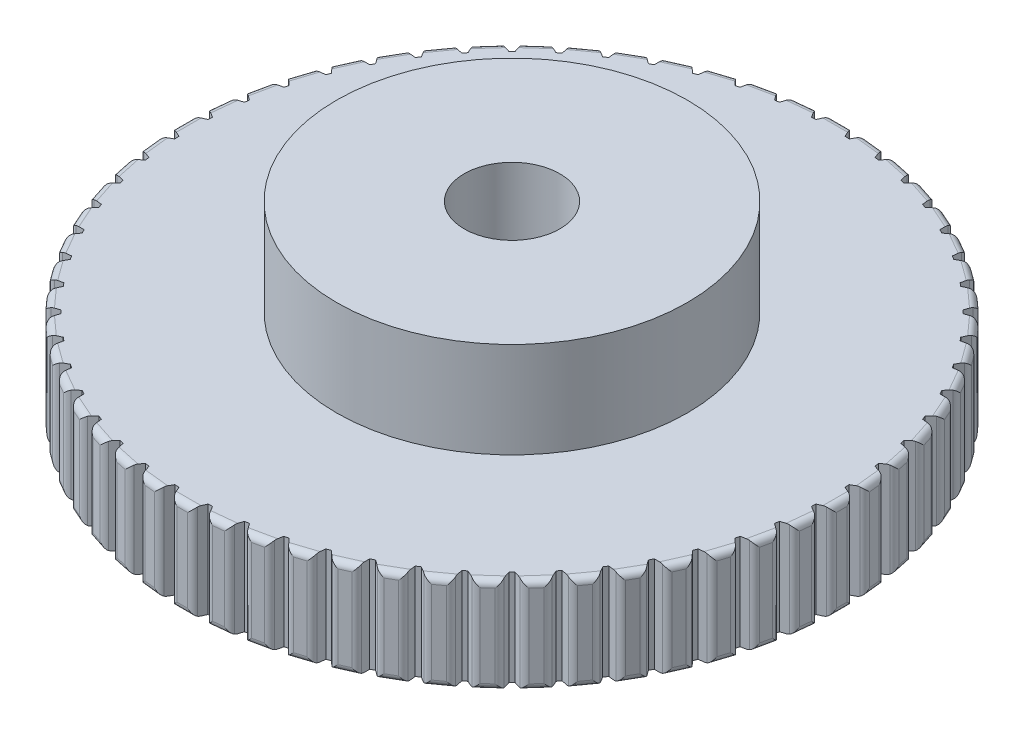
SolidWorks part; units mm, degrees
ref_plane "Front Plane" through (0, 0, 0) normal (0, 0, 1) x (1, 0, 0)
ref_plane "Top Plane" through (0, 0, 0) normal (0, 1, 0) x (1, 0, 0)
ref_plane "Right Plane" through (0, 0, 0) normal (1, 0, 0) x (0, 0, -1)
sketch "Sketch1" plane through (0, 0, 0) normal (0, 1, 0) x (1, 0, 0)
  line L0 (0, -65.659) -> (0, 65.659) construction
  line L1 (0, 65.659) -> (0, 85.595) construction
  line L2 (-1.905, 65.659) -> (1.905, 65.659)
  line L3 (-1.905, 65.659) -> (-3.2908, 62.5134)
  line L4 (-3.2908, 62.5134) -> (3.2908, 62.5134)
  line L5 (3.2908, 62.5134) -> (1.905, 65.659)
  circle A0 centre (0, 0) radius 65.659 construction
  circle A1 centre (0, 0) radius 63.5
  point P9 (0, 62.5134)
  dimension "D1" = 131.318
  dimension "D2" = 127
  dimension "D3" = 3.81
extrude "Boss-Extrude1" add sketch "Sketch1" along normal blind 19.05 contours L3 A1 L5 L4 | L5 A1 L3 L4 region at (0, 0, -62.9849) region at (0, 0, 0.0295)
extrude "Boss-Extrude2" add sketch "Sketch1<3>" along normal blind 19.05 contours A1 L5 L2 L3 region at (0, 0, -64.4954)
sketch "Sketch1<3>" plane through (0, 0, 0) normal (0, 1, 0) x (1, 0, 0) same geometry as "Sketch1"
pattern_circular "CirPattern1" count 60 over 360 about axis through (0, 19.05, 0) along (0, 1, 0) of "Boss-Extrude2"
fillet "Fillet4" radius 1.27 240 edges at (1.905, 9.525, -65.659) (0, 19.05, -65.659) (-1.905, 9.525, -65.659) (0, 0, -65.659) (-4.9687, 9.525, -65.4984) (-6.8632, 19.05, -65.2993) (-8.7578, 9.525, -65.1002) (-6.8632, 0, -65.2993) (-11.7879, 9.525, -64.6203) (-13.6513, 19.05, -64.2242) (-15.5146, 9.525, -63.8281) (-13.6513, 0, -64.2242) (-18.478, 9.525, -63.0341) (-20.2897, 19.05, -62.4454) (-22.1015, 9.525, -61.8567) (-20.2897, 0, -62.4454) (-24.9656, 9.525, -60.7573) (-26.7059, 19.05, -59.9825) (-28.4462, 9.525, -59.2076) (-26.7059, 0, -59.9825) (-31.1797, 9.525, -57.8149) (-32.8295, 19.05, -56.8624) (-34.4793, 9.525, -55.9099) (-32.8295, 0, -56.8624) (-37.0522, 9.525, -54.239) (-38.5934, 19.05, -53.1192) (-40.1346, 9.525, -51.9995) (-38.5934, 0, -53.1192) (-42.5188, 9.525, -50.0688) (-43.9344, 19.05, -48.7941) (-45.3501, 9.525, -47.5195) (-43.9344, 0, -48.7941) (-47.5195, 9.525, -45.3501) (-48.7941, 19.05, -43.9344) (-50.0688, 9.525, -42.5188) (-48.7941, 0, -43.9344) (-51.9995, 9.525, -40.1346) (-53.1192, 19.05, -38.5934) (-54.239, 9.525, -37.0522) (-53.1192, 0, -38.5934) (-55.9099, 9.525, -34.4793) (-56.8624, 19.05, -32.8295) (-57.8149, 9.525, -31.1797) (-56.8624, 0, -32.8295) (-59.2076, 9.525, -28.4462) (-59.9825, 19.05, -26.7059) (-60.7573, 9.525, -24.9656) (-59.9825, 0, -26.7059) (-61.8567, 9.525, -22.1015) (-62.4454, 19.05, -20.2897) (-63.0341, 9.525, -18.478) (-62.4454, 0, -20.2897) (-63.8281, 9.525, -15.5146) (-64.2242, 19.05, -13.6513) (-64.6203, 9.525, -11.7879) (-64.2242, 0, -13.6513) (-65.1002, 9.525, -8.7578) (-65.2993, 19.05, -6.8632) (-65.4984, 9.525, -4.9687) (-65.2993, 0, -6.8632) (-65.659, 9.525, -1.905) (-65.659, 19.05, 0) (-65.659, 9.525, 1.905) (-65.659, 0, 0) (-65.4984, 9.525, 4.9687) (-65.2993, 19.05, 6.8632) (-65.1002, 9.525, 8.7578) (-65.2993, 0, 6.8632) (-64.6203, 9.525, 11.7879) (-64.2242, 19.05, 13.6513) (-63.8281, 9.525, 15.5146) (-64.2242, 0, 13.6513) (-63.0341, 9.525, 18.478) (-62.4454, 19.05, 20.2897) (-61.8567, 9.525, 22.1015) (-62.4454, 0, 20.2897) (-60.7573, 9.525, 24.9656) (-59.9825, 19.05, 26.7059) (-59.2076, 9.525, 28.4462) (-59.9825, 0, 26.7059) (-57.8149, 9.525, 31.1797) (-56.8624, 19.05, 32.8295) (-55.9099, 9.525, 34.4793) (-56.8624, 0, 32.8295) (-54.239, 9.525, 37.0522) (-53.1192, 19.05, 38.5934) (-51.9995, 9.525, 40.1346) (-53.1192, 0, 38.5934) (-50.0688, 9.525, 42.5188) (-48.7941, 19.05, 43.9344) (-47.5195, 9.525, 45.3501) (-48.7941, 0, 43.9344) (-45.3501, 9.525, 47.5195) (-43.9344, 19.05, 48.7941) (-42.5188, 9.525, 50.0688) (-43.9344, 0, 48.7941) (-40.1346, 9.525, 51.9995) (-38.5934, 19.05, 53.1192) (-37.0522, 9.525, 54.239) (-38.5934, 0, 53.1192) (-34.4793, 9.525, 55.9099) (-32.8295, 19.05, 56.8624) (-31.1797, 9.525, 57.8149) (-32.8295, 0, 56.8624) (-28.4462, 9.525, 59.2076) (-26.7059, 19.05, 59.9825) (-24.9656, 9.525, 60.7573) (-26.7059, 0, 59.9825) (-22.1015, 9.525, 61.8567) (-20.2897, 19.05, 62.4454) (-18.478, 9.525, 63.0341) (-20.2897, 0, 62.4454) (-15.5146, 9.525, 63.8281) (-13.6513, 19.05, 64.2242) (-11.7879, 9.525, 64.6203) (-13.6513, 0, 64.2242) (-8.7578, 9.525, 65.1002) (-6.8632, 19.05, 65.2993) (-4.9687, 9.525, 65.4984) (-6.8632, 0, 65.2993) (-1.905, 9.525, 65.659) (0, 19.05, 65.659) (1.905, 9.525, 65.659) (0, 0, 65.659) (4.9687, 9.525, 65.4984) (6.8632, 19.05, 65.2993) (8.7578, 9.525, 65.1002) (6.8632, 0, 65.2993) (11.7879, 9.525, 64.6203) (13.6513, 19.05, 64.2242) (15.5146, 9.525, 63.8281) (13.6513, 0, 64.2242) (18.478, 9.525, 63.0341) (20.2897, 19.05, 62.4454) (22.1015, 9.525, 61.8567) (20.2897, 0, 62.4454) (24.9656, 9.525, 60.7573) (26.7059, 19.05, 59.9825) (28.4462, 9.525, 59.2076) (26.7059, 0, 59.9825) (31.1797, 9.525, 57.8149) (32.8295, 19.05, 56.8624) (34.4793, 9.525, 55.9099) (32.8295, 0, 56.8624) (37.0522, 9.525, 54.239) (38.5934, 19.05, 53.1192) (40.1346, 9.525, 51.9995) (38.5934, 0, 53.1192) (42.5188, 9.525, 50.0688) (43.9344, 19.05, 48.7941) (45.3501, 9.525, 47.5195) (43.9344, 0, 48.7941) (47.5195, 9.525, 45.3501) (48.7941, 19.05, 43.9344) (50.0688, 9.525, 42.5188) (48.7941, 0, 43.9344) (51.9995, 9.525, 40.1346) (53.1192, 19.05, 38.5934) (54.239, 9.525, 37.0522) (53.1192, 0, 38.5934) (55.9099, 9.525, 34.4793) (56.8624, 19.05, 32.8295) (57.8149, 9.525, 31.1797) (56.8624, 0, 32.8295) (59.2076, 9.525, 28.4462) (59.9825, 19.05, 26.7059) (60.7573, 9.525, 24.9656) (59.9825, 0, 26.7059) (61.8567, 9.525, 22.1015) (62.4454, 19.05, 20.2897) (63.0341, 9.525, 18.478) (62.4454, 0, 20.2897) (63.8281, 9.525, 15.5146) (64.2242, 19.05, 13.6513) (64.6203, 9.525, 11.7879) (64.2242, 0, 13.6513) (65.1002, 9.525, 8.7578) (65.2993, 19.05, 6.8632) (65.4984, 9.525, 4.9687) (65.2993, 0, 6.8632) (65.659, 9.525, 1.905) (65.659, 19.05, 0) (65.659, 9.525, -1.905) (65.659, 0, 0) (65.4984, 9.525, -4.9687) (65.2993, 19.05, -6.8632) (65.1002, 9.525, -8.7578) (65.2993, 0, -6.8632) (64.6203, 9.525, -11.7879) (64.2242, 19.05, -13.6513) (63.8281, 9.525, -15.5146) (64.2242, 0, -13.6513) (63.0341, 9.525, -18.478) (62.4454, 19.05, -20.2897) (61.8567, 9.525, -22.1015) (62.4454, 0, -20.2897) (60.7573, 9.525, -24.9656) (59.9825, 19.05, -26.7059) (59.2076, 9.525, -28.4462) (59.9825, 0, -26.7059) (57.8149, 9.525, -31.1797) (56.8624, 19.05, -32.8295) (55.9099, 9.525, -34.4793) (56.8624, 0, -32.8295) (54.239, 9.525, -37.0522) (53.1192, 19.05, -38.5934) (51.9995, 9.525, -40.1346) (53.1192, 0, -38.5934) (50.0688, 9.525, -42.5188) (48.7941, 19.05, -43.9344) (47.5195, 9.525, -45.3501) (48.7941, 0, -43.9344) (45.3501, 9.525, -47.5195) (43.9344, 19.05, -48.7941) (42.5188, 9.525, -50.0688) (43.9344, 0, -48.7941) (40.1346, 9.525, -51.9995) (38.5934, 19.05, -53.1192) (37.0522, 9.525, -54.239) (38.5934, 0, -53.1192) (34.4793, 9.525, -55.9099) (32.8295, 19.05, -56.8624) (31.1797, 9.525, -57.8149) (32.8295, 0, -56.8624) (28.4462, 9.525, -59.2076) (26.7059, 19.05, -59.9825) (24.9656, 9.525, -60.7573) (26.7059, 0, -59.9825) (22.1015, 9.525, -61.8567) (20.2897, 19.05, -62.4454) (18.478, 9.525, -63.0341) (20.2897, 0, -62.4454) (15.5146, 9.525, -63.8281) (13.6513, 19.05, -64.2242) (11.7879, 9.525, -64.6203) (13.6513, 0, -64.2242) (8.7578, 9.525, -65.1002) (6.8632, 19.05, -65.2993) (4.9687, 9.525, -65.4984) (6.8632, 0, -65.2993)
sketch "Sketch2" plane through (0, 19.05, 0) normal (0, 1, 0) x (1, 0, 0)
  circle A0 centre (0, 0) radius 34.925
  dimension "D1" = 69.85
extrude "Boss-Extrude3" add sketch "Sketch2" along normal blind 19.05
sketch "Sketch3" plane through (0, 38.1, 0) normal (0, 1, 0) x (1, 0, 0)
  circle A0 centre (0, 0) radius 9.525
  dimension "D1" = 19.05
extrude "Cut-Extrude1" cut sketch "Sketch3" against normal through all contours A0
